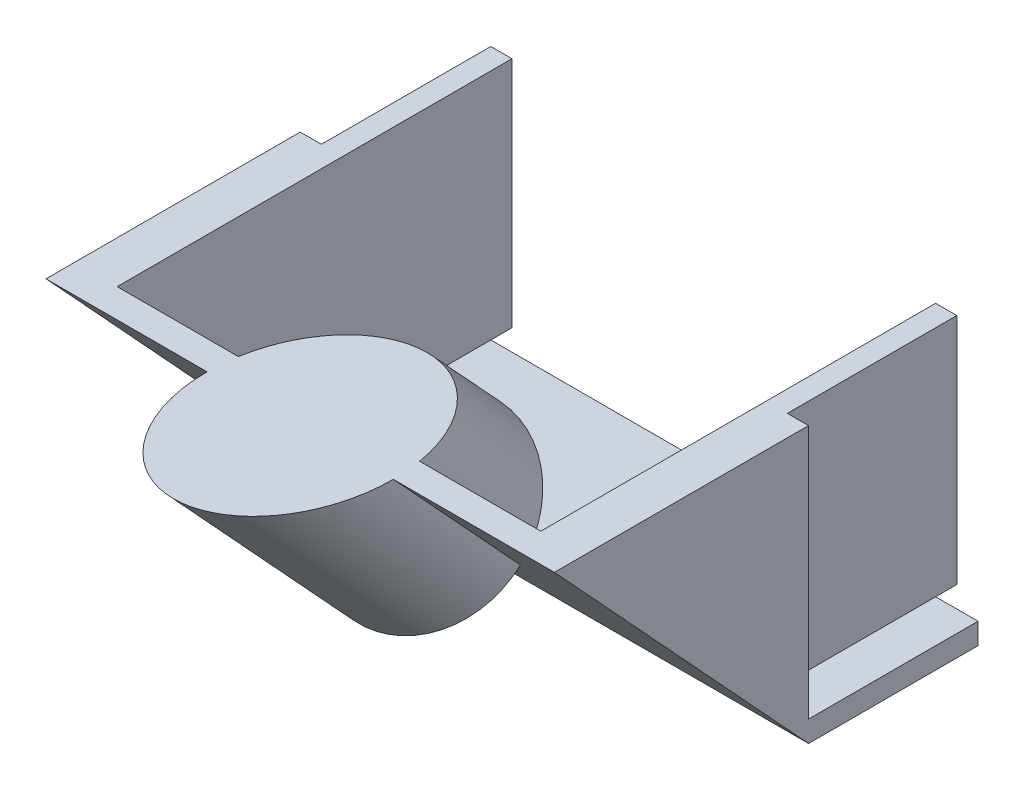
SolidWorks part; units mm, degrees
ref_plane "Front Plane" through (0, 0, 0) normal (0, 0, 1) x (1, 0, 0)
ref_plane "Top Plane" through (0, 0, 0) normal (0, 1, 0) x (1, 0, 0)
ref_plane "Right Plane" through (0, 0, 0) normal (1, 0, 0) x (0, 0, -1)
sketch "Sketch4" plane through (0, 0, 0) normal (1, 0, 0) x (0, 0, -1)
  line L0 (0, 0) -> (0, 82.55)
  line L5 (0, 82.55) -> (-76.2, 82.55)
  line L6 (-76.2, 82.55) -> (0, 0)
  line L21 (0, 0) -> (0, 6.35)
  line L25 (0, 76.2) -> (0, 12.7)
  dimension "D1" = 82.55
  dimension "D2" = 76.2
extrude "Boss-Extrude2" add sketch "Sketch4" along normal blind 76.2 and the other way blind 76.2 contours L6 L0 L5
sketch "Sketch6" plane through (0, 0, 0) normal (0, 0, -1) x (-1, 0, 0)
  line L0 (76.2, 0) -> (76.2, 82.55) construction
  line L1 (-76.2, 0) -> (76.2, 0)
  line L2 (-76.2, 0) -> (-76.2, 6.35)
  line L3 (-76.2, 6.35) -> (76.2, 6.35)
  line L4 (76.2, 0) -> (76.2, 6.35)
  line L5 (76.2, 82.55) -> (-76.2, 82.55) construction
  line L6 (-69.85, 82.55) -> (-63.5, 82.55)
  line L7 (-69.85, 82.55) -> (-69.85, 12.7)
  line L8 (-69.85, 12.7) -> (-63.5, 12.7)
  line L9 (-63.5, 82.55) -> (-63.5, 12.7)
  line L10 (0, 0) -> (0, 82.55) construction
  line L11 (69.85, 12.7) -> (63.5, 12.7)
  line L12 (63.5, 82.55) -> (63.5, 12.7)
  line L13 (69.85, 82.55) -> (63.5, 82.55)
  line L14 (69.85, 82.55) -> (69.85, 12.7)
  dimension "D1" = 6.35
  dimension "D2" = 139.7
  dimension "D3" = 6.35
  dimension "D4" = 6.35
extrude "Boss-Extrude3" add sketch "Sketch6" along normal blind 50.8
sketch "Sketch7" plane through (0, 0, 0) normal (0, 0, -1) x (-1, 0, 0)
  line L1 (-63.5, 82.55) -> (63.5, 82.55)
  line L2 (-63.5, 82.55) -> (-63.5, 12.7)
  line L3 (-63.5, 12.7) -> (63.5, 12.7)
  line L4 (63.5, 82.55) -> (63.5, 12.7)
extrude "Cut-Extrude3" cut sketch "Sketch7" against normal offset from surface (67.5582 mm away) 6.35 up to face at (0, 41.275, 38.1)
ref_plane "Plane1" through (0, 41.275, 38.1) normal (0, -0.7348, -0.6783) x (-1, 0, 0)
sketch "Sketch8" plane through (0, 41.275, 38.1) normal (0, -0.7348, -0.6783) x (-1, 0, 0)
  circle A0 centre (0, 0) radius 27.915
extrude "Boss-Extrude4" add sketch "Sketch8" against normal up to surface (30.4038 mm away) up to face at (0, 82.55, 7.0264)
equation "\"t\"= .005in"
